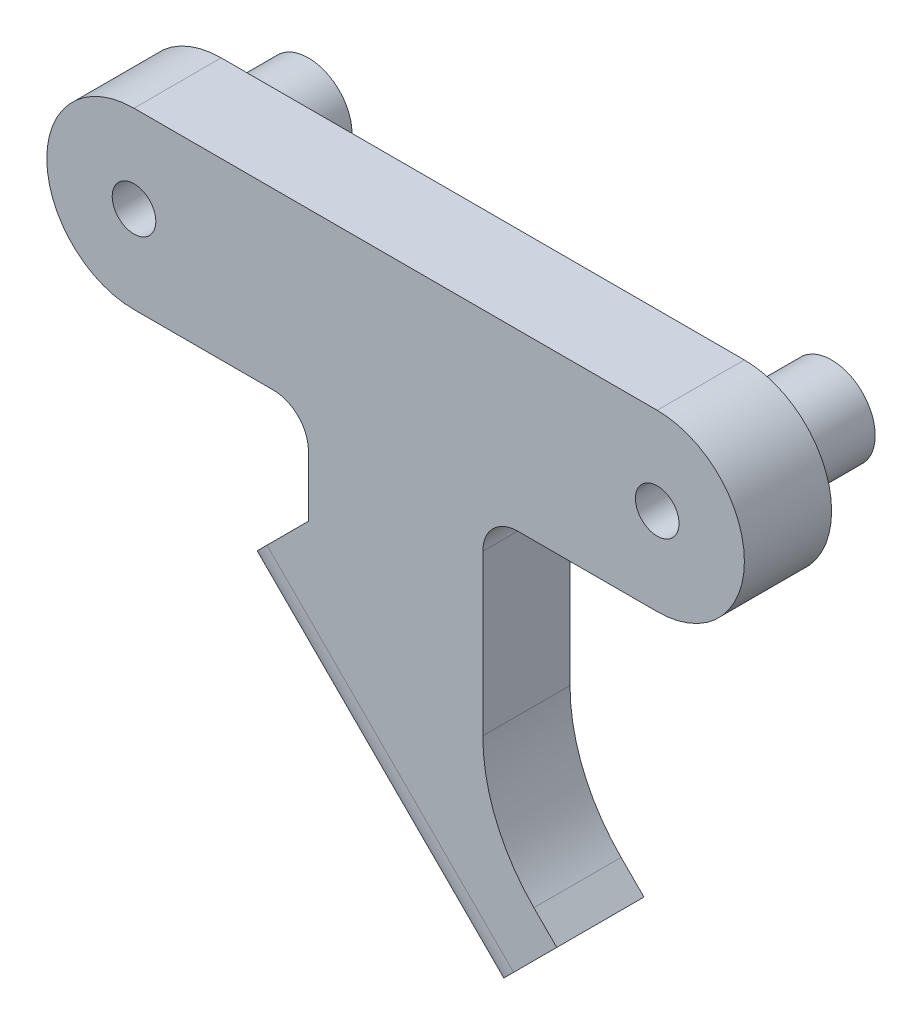
SolidWorks part; units mm, degrees
material "PET"
ref_plane "Piano frontale" through (0, 0, 0) normal (0, 0, 1) x (1, 0, 0)
ref_plane "Piano superiore" through (0, 0, 0) normal (0, 1, 0) x (1, 0, 0)
ref_plane "Piano destro" through (0, 0, 0) normal (1, 0, 0) x (0, 0, -1)
sketch "Schizzo1" plane through (0, 0, 0) normal (0, 0, 1) x (1, 0, 0)
  line L1 (-13.208, 5) -> (16.792, 5)
  line L2 (-13.208, -5) -> (-3.208, -5)
  line L3 (6.792, -28.7941) -> (6.792, -18.7941)
  line L4 (-3.208, -18.7941) -> (6.792, -28.7941)
  line L5 (6.792, -5) -> (16.792, -5)
  line L7 (-3.208, -5) -> (-3.208, -18.7941)
  line L9 (6.792, -5) -> (6.792, -18.7941)
  line L10 (6.792, 0) -> (16.792, 0) construction
  arc A0 (-13.208, 5) -> (-13.208, -5) centre (-13.208, 0) ccw
  arc A1 (16.792, -5) -> (16.792, 5) centre (16.792, 0) ccw
  point P3 (1.792, 0)
  dimension "D1" = 30
  dimension "D2" = 10
  dimension "D3" = 10
  dimension "D4" = 10
extrude "Estrusione-Estrusione3" add sketch "Schizzo1" along normal blind 5 contours L2 L7 L4 L3 L9 L5 A1 L1 A0
sketch "Schizzo3" plane through (0, 0, 0) normal (0, 0, -1) x (-1, 0, 0)
  line L6 (13.208, 5) -> (-16.792, 5)
  line L7 (-16.792, -5) -> (-6.792, -5)
  line L8 (-6.792, -5) -> (-6.792, -28.7941)
  line L9 (-6.792, -28.7941) -> (3.208, -18.7941)
  line L10 (3.208, -18.7941) -> (3.208, -5)
  line L11 (3.208, -5) -> (13.208, -5)
  line L12 (13.208, 5) -> (-16.792, 5) construction
  line L13 (-16.792, -5) -> (-6.792, -5) construction
  line L14 (-6.792, -5) -> (-6.792, -28.7941) construction
  line L15 (-6.792, -28.7941) -> (3.208, -18.7941) construction
  line L16 (3.208, -18.7941) -> (3.208, -5) construction
  line L17 (3.208, -5) -> (13.208, -5) construction
  circle A0 centre (-16.792, 0) radius 2.5
  circle A1 centre (13.208, 0) radius 2.5
  arc A2 (13.208, -5) -> (13.208, 5) centre (13.208, 0) ccw
  arc A3 (-16.792, 5) -> (-16.792, -5) centre (-16.792, 0) ccw
  arc A4 (13.208, -5) -> (13.208, 5) centre (13.208, 0) ccw construction
  arc A5 (-16.792, 5) -> (-16.792, -5) centre (-16.792, 0) ccw construction
  dimension "D1" = 0
extrude "Estrusione-Estrusione4" add sketch "Schizzo3" along normal blind 5
ref_plane "Piano1" through (17.7931, -17.7931, 0) normal (-0.7071, 0.7071, 0) x (0, 0, -1)
sketch "Schizzo7" plane through (17.7931, -17.7931, 0) normal (-0.7071, 0.7071, 0) x (0, 0, -1)
  line L0 (-5, 15.5578) -> (-5, -1.2671) construction
  line L1 (0, 15.5578) -> (-5, 15.5578)
  line L2 (0, 15.5578) -> (0, 9.5578)
  line L3 (0, 9.5578) -> (-5, 9.5578)
  line L4 (-5, 15.5578) -> (-5, 9.5578)
  dimension "D1" = 6
extrude "Estrusione-Estrusione5" add sketch "Schizzo7" along normal blind 20
sketch "Schizzo6" plane through (17.7931, -17.7931, 0) normal (-0.7071, 0.7071, 0) x (0, 0, -1)
  line L0 (0, -1.2671) -> (0, 9.5578) construction
  line L1 (-5, 15.5578) -> (0, 15.5578) construction
  circle A0 centre (-2.5, 12.5578) radius 1.65
  dimension "D1" = 3.3
  dimension "D2" = 2.5
  dimension "D3" = 3
extrude "Taglio-Estrusione1" cut sketch "Schizzo6" along normal up to surface (20 mm away) up to face at (-5.2791, -12.5809, 2.5)
fillet "Raccordo1" radius 2.5 2 edges at (-0.2791, -21.723, 0) (-0.2791, -21.723, 5)
sketch "Schizzo8" plane through (0, 0, -5) normal (0, 0, -1) x (-1, 0, 0)
  circle A0 centre (-16.792, 0) radius 1.25
  circle A1 centre (13.208, 0) radius 1.25
  dimension "D1" = 2.5
extrude "Taglio-Estrusione2" cut sketch "Schizzo8" against normal through all
fillet "Raccordo2" radius 2 2 edges at (-3.208, -5, 2.5) (6.792, -5, 2.5)
fillet "Raccordo3" radius 10 1 edges at (6.792, -20.3088, 2.5)
ref_axis "Assi1" through (-5.2288, -12.5306, 2.5) along (0.7071, -0.7071, 0)
ref_point "Punto1"
ref_axis "Assi2" through (11.0346, -24.5515, 5) along (0, 0, -1)
ref_point "Punto2"
ref_axis "Assi3" through (16.792, 0, 5) along (0, 0, -1)
ref_axis "Assi4" through (6.792, -7, 0) along (0, -1, 0)
ref_point "Punto3"
sketch "Schizzo9" plane through (0, 0, 0) normal (0, 0, -1) x (-1, 0, 0)
  line L0 (-16.792, 0) -> (13.208, 0)
  line L1 (-1.792, 0) -> (-1.792, -20.2586)
  line L2 (-8.5598, -27.0263) -> (5.5824, -12.8842) construction
  point P4 (-1.792, 0)
  point P5 (0, 0)
ref_point "Punto4"
